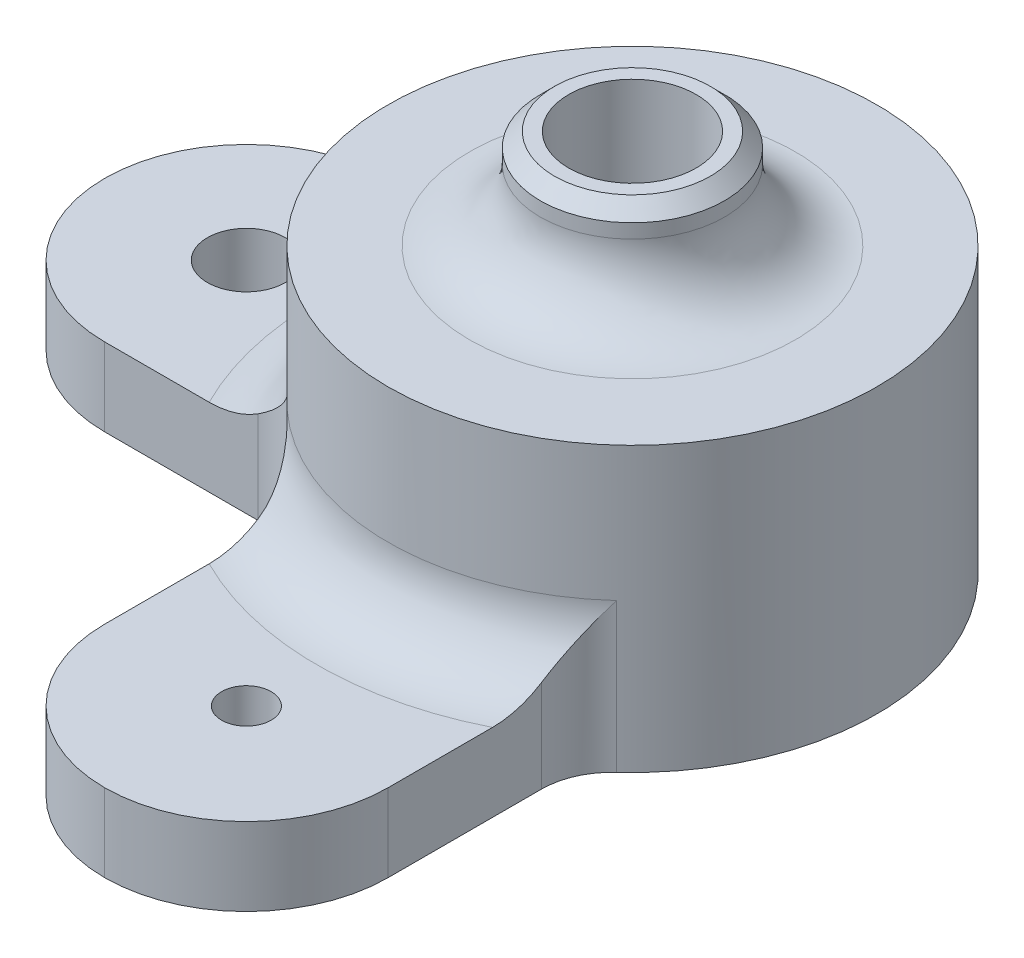
SolidWorks part; units mm, degrees
ref_plane "Plano frontal" through (0, 0, 0) normal (0, 0, 1) x (1, 0, 0)
ref_plane "Plano superior" through (0, 0, 0) normal (0, 1, 0) x (1, 0, 0)
ref_plane "Plano direito" through (0, 0, 0) normal (1, 0, 0) x (0, 0, -1)
sketch "Esboço1" plane through (0, 0, 0) normal (0, 1, 0) x (1, 0, 0)
  line L1 (0, -7.7942) -> (6.75, -3.8971)
  line L2 (6.75, -3.8971) -> (6.75, 3.8971)
  line L3 (6.75, 3.8971) -> (0, 7.7942)
  line L4 (0, 7.7942) -> (-6.75, 3.8971)
  line L5 (-6.75, 3.8971) -> (-6.75, -3.8971)
  line L6 (-6.75, -3.8971) -> (0, -7.7942)
  circle A0 centre (0, 0) radius 11.25
  circle A1 centre (0, 0) radius 17.25
  circle A2 centre (0, 0) radius 6.75 construction
  circle A3 centre (0, 0) radius 4.5
  dimension "D1" = 22.5
  dimension "D2" = 6
  dimension "D3" = 13.5
  dimension "D4" = 9
extrude "Ressalto-extrusão1" add sketch "Esboço1" along normal blind 20 contours A3 | A1 region at (0, 0, 0)
extrude "Corte-extrusão1" cut sketch "Esboço1<3>" along normal blind 8 contours L5 L6 L1 L2 L3 L4 region at (-3.2719, 0, 5.6671)
sketch "Esboço1<3>" plane through (0, 0, 0) normal (0, 1, 0) x (1, 0, 0) same geometry as "Esboço1"
sketch "Esboço5" plane through (0, 0, 0) normal (0, -1, 0) x (1, 0, 0)
  line L0 (0, 0) -> (-27.25, 0) construction
  line L1 (-17.25, 10) -> (-14.0557, 10)
  line L2 (-37.25, 10) -> (-17.25, 10)
  line L3 (-37.25, 10) -> (-37.25, -10)
  line L4 (-37.25, -10) -> (-17.25, -10)
  line L5 (-17.25, 10) -> (-17.25, -10) construction
  line L6 (-37.25, 10) -> (-17.25, -10) construction
  line L7 (-37.25, -10) -> (-17.25, 10) construction
  line L8 (-17.25, -10) -> (-14.0557, -10)
  line L9 (0, 0) -> (0, 27.25) construction
  line L10 (-10, 17.25) -> (-10, 14.0557)
  line L11 (-10, 37.25) -> (10, 37.25)
  line L12 (-10, 37.25) -> (-10, 17.25)
  line L13 (-10, 17.25) -> (10, 17.25) construction
  line L14 (10, 37.25) -> (10, 17.25)
  line L15 (-10, 37.25) -> (10, 17.25) construction
  line L16 (-10, 17.25) -> (10, 37.25) construction
  line L17 (10, 17.25) -> (10, 14.0557)
  circle A0 centre (0, 0) radius 17.25 construction
  circle A2 centre (-27.25, 0) radius 2.75
  arc A3 (10, 14.0557) -> (-10, 14.0557) centre (0, 0) ccw
  circle A4 centre (0, 0) radius 17.25
  arc A5 (-14.0557, 10) -> (-14.0557, -10) centre (0, 0) ccw
  circle A6 centre (0, 27.25) radius 1.75
  dimension "D3" = 5.5
  dimension "D7" = 3.5
  dimension "D1" = 20
  dimension "D2" = 20
  dimension "D4" = 20
  dimension "D5" = 20
  dimension "D6" = 0
extrude "Ressalto-extrusão2" add sketch "Esboço5" against normal blind 5.5
fillet "Filete1" radius 5 6 edges at (-14.0557, 2.75, 10) (-14.0557, 2.75, -10) (-17.25, 5.5, 0) (0, 5.5, 17.25) (10, 2.75, 14.0557) (-10, 2.75, 14.0557)
fillet "Filete2" radius 10 4 edges at (10, 2.75, 37.25) (-10, 2.75, 37.25) (-37.25, 2.75, -10) (-37.25, 2.75, 10)
sketch "Esboço6" plane through (0, 20, 0) normal (0, 1, 0) x (1, 0, 0)
  circle A0 centre (0, 0) radius 100
  dimension "D1" = 200
sketch "Esboço7" plane through (0, 20, 0) normal (0, 1, 0) x (1, 0, 0)
  circle A0 centre (0, 0) radius 6.5
  circle A1 centre (0, 0) radius 4.5 construction
  circle A2 centre (0, 0) radius 4.5
  dimension "D1" = 2
extrude "Ressalto-extrusão3" add sketch "Esboço7" along normal blind 7
fillet "Filete3" radius 5 1 edges at (0, 20, 6.5)
chamfer "Chanfro1" distance 1 angle 45 1 edges at (0, 27, 6.5)
